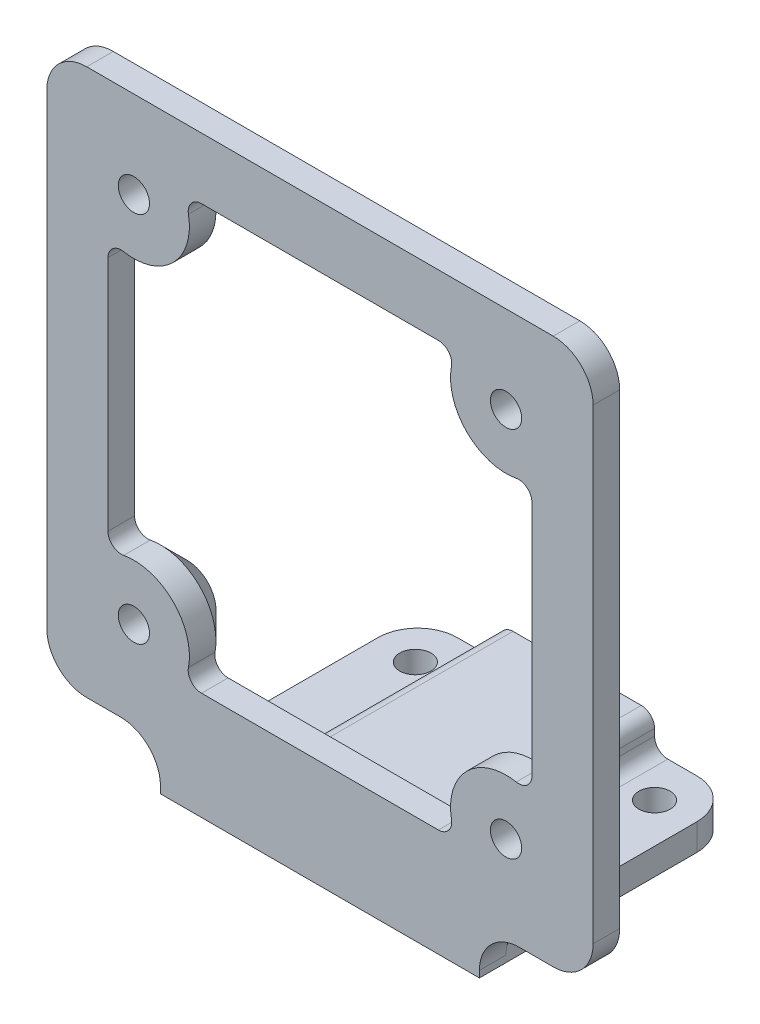
SolidWorks part; units mm, degrees
ref_plane "Front Plane" through (0, 0, 0) normal (0, 0, 1) x (1, 0, 0)
ref_plane "Top Plane" through (0, 0, 0) normal (0, 1, 0) x (1, 0, 0)
ref_plane "Right Plane" through (0, 0, 0) normal (1, 0, 0) x (0, 0, -1)
ref_plane "Plane1" through (0, 0, -4) normal (0, 0, 1) x (1, 0, 0)
sketch "Sketch1" plane through (0, 0, 0) normal (0, 0, 1) x (1, 0, 0)
  line L0 (-19.05, 5) -> (19.05, 5) construction
  line L1 (-19.05, 43.1) -> (-19.05, 5) construction
  line L2 (19.05, 43.1) -> (-19.05, 43.1) construction
  line L3 (19.05, 5) -> (19.05, 43.1) construction
  line L4 (-19.05, 5) -> (19.05, 5)
  line L5 (-19.05, 43.1) -> (-19.05, 5)
  line L6 (19.05, 43.1) -> (-19.05, 43.1)
  line L7 (19.05, 5) -> (19.05, 43.1)
  line L8 (15.95, 18.225) -> (15.95, 29.875) construction
  line L9 (-15.95, 29.875) -> (-15.95, 18.225) construction
  line L10 (8.4, 8.1) -> (14, 8.1) construction
  line L11 (-14, 8.1) -> (-8.4, 8.1) construction
  line L12 (-8.4, 40) -> (-14, 40) construction
  line L13 (14, 40) -> (8.4, 40) construction
  line L14 (15.95, 18.225) -> (15.95, 29.875)
  line L15 (-15.95, 29.875) -> (-15.95, 18.225)
  line L16 (8.4, 8.1) -> (14, 8.1)
  line L17 (-14, 8.1) -> (-8.4, 8.1)
  line L18 (-8.4, 40) -> (-14, 40)
  line L19 (14, 40) -> (8.4, 40)
  arc A0 (-17.05, 8.349) -> (-15.701, 7) centre (-17, 7.05) ccw construction
  arc A1 (-15.701, 41.1) -> (-17.05, 39.751) centre (-17, 41.05) ccw construction
  arc A2 (17.05, 39.751) -> (15.701, 41.1) centre (17, 41.05) ccw construction
  arc A3 (15.701, 7) -> (17.05, 8.349) centre (17, 7.05) ccw construction
  arc A4 (-17.05, 8.349) -> (-15.701, 7) centre (-17, 7.05) ccw
  arc A5 (-15.701, 41.1) -> (-17.05, 39.751) centre (-17, 41.05) ccw
  arc A6 (17.05, 39.751) -> (15.701, 41.1) centre (17, 41.05) ccw
  arc A7 (15.701, 7) -> (17.05, 8.349) centre (17, 7.05) ccw
  circle A8 centre (14, 10.05) radius 1.4 construction
  circle A9 centre (-14, 10.05) radius 1.4 construction
  circle A10 centre (-14, 38.05) radius 1.4 construction
  circle A11 centre (14, 38.05) radius 1.4 construction
  circle A12 centre (14, 10.05) radius 1.4
  circle A13 centre (-14, 10.05) radius 1.4
  circle A14 centre (-14, 38.05) radius 1.4
  circle A15 centre (14, 38.05) radius 1.4
sketch "Sketch2" plane through (0, 0, 0) normal (0, 1, 0) x (1, 0, 0)
  line L4 (12, 40.175) -> (-12, 40.175)
  line L5 (-12, 40.175) -> (-12, 2.175)
  line L6 (-12, 2.175) -> (12, 2.175)
  line L7 (12, 2.175) -> (12, 40.175)
  line L8 (12, 40.175) -> (-12, 40.175)
  line L9 (-12, 40.175) -> (-12, 2.175)
  line L10 (-12, 2.175) -> (12, 2.175)
  line L11 (12, 2.175) -> (12, 40.175)
  circle A1 centre (9, 16.175) radius 1.175
  circle A2 centre (9, 16.175) radius 1.175
  circle A3 centre (9, 5.175) radius 1.175
  circle A4 centre (9, 5.175) radius 1.175
  circle A5 centre (-9, 5.175) radius 1.175
  circle A6 centre (-9, 5.175) radius 1.175
  circle A7 centre (-9, 16.175) radius 1.175
  circle A8 centre (-9, 16.175) radius 1.175
  point P14 (0, 0)
  dimension "D1" = 0
  dimension "D2" = 0
  dimension "D3" = 0
  dimension "D4" = 0
  dimension "D5" = 0
sketch "Sketch3" plane through (0, 0, 0) normal (0, 0, 1) x (1, 0, 0)
  line L0 (-19.05, 5) -> (19.05, 5) construction
  line L1 (19.05, 5) -> (19.05, 43.1) construction
  line L2 (19.05, 43.1) -> (-19.05, 43.1) construction
  line L3 (-19.05, 43.1) -> (-19.05, 5) construction
  line L4 (-19.05, 5) -> (19.05, 5) construction
  line L5 (19.05, 5) -> (19.05, 43.1) construction
  line L6 (19.05, 43.1) -> (-19.05, 43.1) construction
  line L7 (-19.05, 43.1) -> (-19.05, 5) construction
  line L8 (-20.55, 3.5) -> (-12, 3.5)
  line L9 (20.55, 3.5) -> (20.55, 44.6)
  line L10 (20.55, 44.6) -> (-20.55, 44.6)
  line L11 (-20.55, 44.6) -> (-20.55, 3.5)
  line L14 (-12, 0) -> (-12, 3.5)
  line L15 (-12, 0) -> (12, 0) construction
  line L16 (12, 0) -> (-12, 0) construction
  line L17 (-12, 0) -> (12, 0)
  line L18 (12, 0) -> (12, 3.5)
  line L19 (12, 3.5) -> (20.55, 3.5)
  line L20 (-20.55, 3.5) -> (20.55, 3.5) construction
  circle A0 centre (14, 38.05) radius 1.175
  circle A1 centre (-14, 38.05) radius 1.175
  circle A2 centre (-14, 10.05) radius 1.175
  circle A3 centre (14, 10.05) radius 1.175
  point P27 (0, 0)
  point P30 (0, 0)
  dimension "D2" = 2.35
  dimension "D1" = 1.5
extrude "Boss-Extrude1" add sketch "Sketch3" against normal blind 2
fillet "Fillet1" radius 3 2 edges at (-12, 3.5, -1) (12, 3.5, -1)
sketch "Sketch4" plane through (0, 0, 0) normal (0, -1, 0) x (1, 0, 0)
  line L1 (-12, 0) -> (12, 0)
  line L2 (-12, 0) -> (-12, -19.35)
  line L3 (-12, -19.35) -> (12, -19.35)
  line L4 (12, 0) -> (12, -19.35)
  circle A0 centre (9, -16.175) radius 1.175 construction
  circle A1 centre (-9, -16.175) radius 1.175 construction
  circle A2 centre (-9, -5.175) radius 1.175 construction
  circle A3 centre (9, -5.175) radius 1.175 construction
  circle A4 centre (9, -16.175) radius 1.175
  circle A5 centre (-9, -16.175) radius 1.175
  circle A6 centre (-9, -5.175) radius 1.175
  circle A7 centre (9, -5.175) radius 1.175
  point P5 (10.1018, -15.5833)
  point P7 (9, -17.35)
  dimension "D1" = 2
extrude "Boss-Extrude2" add sketch "Sketch4" against normal blind 2
fillet "Fillet2" radius 3 6 edges at (-20.55, 44.6, -1) (-20.55, 3.5, -1) (20.55, 3.5, -1) (20.55, 44.6, -1) (12, 1, -19.35) (-12, 1, -19.35)
sketch "Sketch5" plane through (0, 0, -2) normal (0, 0, -1) x (-1, 0, 0)
  circle A0 centre (14, 10.05) radius 1.175 construction
  circle A1 centre (-14, 10.05) radius 1.175 construction
  circle A2 centre (-14, 38.05) radius 1.175 construction
  circle A3 centre (14, 38.05) radius 1.175 construction
  circle A4 centre (14, 10.05) radius 1.175
  circle A5 centre (-14, 10.05) radius 1.175
  circle A6 centre (-14, 38.05) radius 1.175
  circle A7 centre (14, 38.05) radius 1.175
  circle A8 centre (14, 10.05) radius 2.175
  circle A9 centre (-14, 10.05) radius 2.175
  circle A10 centre (-14, 38.05) radius 2.175
  circle A11 centre (14, 38.05) radius 2.175
  dimension "D1" = 1
extrude "Boss-Extrude3" add sketch "Sketch5" along normal up to surface (2 mm away) up to plane "Plane1"
chamfer "Chamfer2" distance 2 angle 45 4 edges at (-11.825, 10.05, -2) (16.175, 10.05, -2) (-11.825, 38.05, -2) (16.175, 38.05, -2)
sketch "Sketch6" plane through (0, 0, 0) normal (0, 0, 1) x (1, 0, 0)
  line L0 (14, 40) -> (8.4, 40) construction
  line L1 (-10.3084, 40) -> (10.3084, 40)
  line L2 (-15.95, 34.3584) -> (-15.95, 13.7416)
  line L3 (-10.3084, 8.1) -> (10.3084, 8.1)
  line L4 (15.95, 34.3584) -> (15.95, 13.7416)
  line L5 (15.95, 18.225) -> (15.95, 29.875) construction
  line L6 (-15.95, 29.875) -> (-15.95, 18.225) construction
  line L7 (8.4, 8.1) -> (14, 8.1) construction
  circle A0 centre (-14, 38.05) radius 4.175 construction
  circle A1 centre (-14, 10.05) radius 4.175 construction
  circle A2 centre (14, 10.05) radius 4.175 construction
  circle A3 centre (14, 38.05) radius 4.175 construction
  arc A4 (-15.95, 34.3584) -> (-10.3084, 40) centre (-14, 38.05) ccw
  arc A5 (-10.3084, 8.1) -> (-15.95, 13.7416) centre (-14, 10.05) ccw
  arc A6 (15.95, 13.7416) -> (10.3084, 8.1) centre (14, 10.05) ccw
  arc A7 (10.3084, 40) -> (15.95, 34.3584) centre (14, 38.05) ccw
extrude "Cut-Extrude1" cut sketch "Sketch6" against normal up to next
fillet "Fillet3" radius 1 8 edges at (-15.95, 13.7416, -1) (-10.3084, 8.1, -1) (10.3084, 8.1, -1) (15.95, 13.7416, -1) (15.95, 34.3584, -1) (10.3084, 40, -1) (-10.3084, 40, -1) (-15.95, 34.3584, -1)
sketch "Sketch7" plane through (0, 0, -2) normal (0, 0, -1) x (-1, 0, 0)
  line L0 (-7.825, 2) -> (-10.175, 2) construction
  line L1 (10.175, 2) -> (7.825, 2) construction
  line L2 (-7.825, 2) -> (-10.175, 2) construction
  line L3 (10.175, 2) -> (7.825, 2) construction
  line L4 (19.05, 5) -> (-19.05, 5) construction
  line L5 (19.05, 5) -> (-19.05, 5) construction
  line L6 (12, 2) -> (-12, 2) construction
  line L7 (-5.825, 4.5) -> (5.825, 4.5)
  line L8 (-5.825, 4.5) -> (-5.825, 2)
  line L9 (-5.825, 2) -> (5.825, 2)
  line L10 (5.825, 4.5) -> (5.825, 2)
  point P12 (32.1739, 2)
  point P13 (0, 5)
  point P14 (0, 2)
  dimension "D1" = 0.5
  dimension "D2" = 2
extrude "Boss-Extrude4" add sketch "Sketch7" along normal through all
fillet "Fillet4" radius 1 4 edges at (-5.825, 2, -10.675) (5.825, 2, -10.675) (-5.825, 4.5, -10.675) (5.825, 4.5, -10.675)
chamfer "Chamfer3" distance 1 angle 45 9 edges at (-9.4125, 2, -2) (-6.1179, 2.2929, -2) (-5.825, 3.25, -2) (-5.5321, 4.2071, -2) (0, 4.5, -2) (5.5321, 4.2071, -2) (5.825, 3.25, -2) (6.1179, 2.2929, -2) (9.4125, 2, -2)
